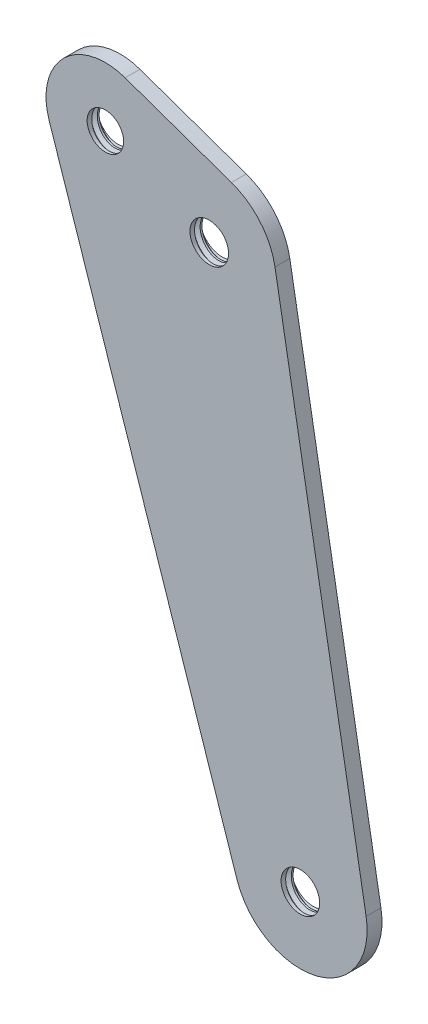
SolidWorks part; units mm, degrees
material "AISI 304"
ref_plane "Alzado" through (0, 0, 0) normal (0, 0, 1) x (1, 0, 0)
ref_plane "Planta" through (0, 0, 0) normal (0, 1, 0) x (1, 0, 0)
ref_plane "Vista lateral" through (0, 0, 0) normal (1, 0, 0) x (0, 0, -1)
ref_plane "Plano1" through (0, 0, 4.2) normal (0, 0, 1) x (1, 0, 0)
sketch "Sk_Placa_jaula_exterior" plane through (0, 0, 4.2) normal (0, 0, 1) x (1, 0, 0)
  line L0 (-43.5893, -64.5304) -> (-18.2523, -140.5219)
  line L1 (-0.8511, -136.1123) -> (-13.1367, -66.4372)
  line L2 (-19.0055, -59.5128) -> (-33.3382, -54.4558)
  arc A0 (-18.2523, -140.5219) -> (-0.8511, -136.1123) centre (-9.7144, -137.6751) ccw
  arc A1 (-13.1367, -66.4372) -> (-19.0055, -59.5128) centre (-22, -68) ccw
  arc A2 (-33.3382, -54.4558) -> (-43.5893, -64.5304) centre (-36, -62) ccw
  circle A3 centre (-36, -62) radius 2.46
  circle A4 centre (-22, -68) radius 2.6
  circle A5 centre (-9.7144, -137.6751) radius 2.6
extrude "Placa_jaula_exterior" add sketch "Sk_Placa_jaula_exterior" along normal blind 2
thread "Rosca_M6x1" pitch 1 method cut profile "Perfil de rosca1" start angle 135, offset 0, length 2, pitch 1, diameter 4.92
ref_plane "Plano2" through (-34.2605, -60.2605, 6.2) normal (-0.7071, 0.7071, 0) x (0.7071, 0.7071, 0)
sketch "Perfil de rosca1" plane through (-34.2605, -60.2605, 6.2) normal (-0.7071, 0.7071, 0) x (0.7071, 0.7071, 0)
  line L0 (0, 0) -> (0, 1) construction
  line L1 (0, 0) -> (0.5413, 0.3125)
  line L2 (0.5413, 0.3125) -> (0.5413, 0.4375)
  line L3 (0.5413, 0.4375) -> (0, 0.75)
  line L4 (0.5413, 0.375) -> (0, 0.375) construction
  line L11 (0, 0) -> (0, 0.75)
  point P2 (0, 0)
  dimension "Pitch" = 1
  dimension "Profile_Angle" = 60
  dimension "Profile_Land" = 0.125
  dimension "Profile_Height" = 0.5413
thread "Rosca1" pitch 1 method cut profile "Perfil de rosca2" start angle 135, offset 0, length 2, pitch 1, diameter 5.2
ref_plane "Plano3" through (-7.8759, -135.8367, 6.2) normal (-0.7071, 0.7071, 0) x (0.7071, 0.7071, 0)
sketch "Perfil de rosca2" plane through (-7.8759, -135.8367, 6.2) normal (-0.7071, 0.7071, 0) x (0.7071, 0.7071, 0)
  line L0 (0, 0) -> (0, 1) construction
  line L1 (0, 0) -> (0.5413, 0.3125)
  line L2 (0.5413, 0.3125) -> (0.5413, 0.4375)
  line L3 (0.5413, 0.4375) -> (0, 0.75)
  line L4 (0.5413, 0.375) -> (0, 0.375) construction
  line L11 (0, 0) -> (0, 0.75)
  point P2 (0, 0)
  dimension "Pitch" = 1
  dimension "Profile_Angle" = 60
  dimension "Profile_Land" = 0.125
  dimension "Profile_Height" = 0.5413
thread "Rosca2" pitch 1 method cut profile "Perfil de rosca3" start angle 135, offset 0, length 2, pitch 1, diameter 5.2
ref_plane "Plano4" through (-20.1615, -66.1615, 6.2) normal (-0.7071, 0.7071, 0) x (0.7071, 0.7071, 0)
sketch "Perfil de rosca3" plane through (-20.1615, -66.1615, 6.2) normal (-0.7071, 0.7071, 0) x (0.7071, 0.7071, 0)
  line L0 (0, 0) -> (0, 1) construction
  line L1 (0, 0) -> (0.5413, 0.3125)
  line L2 (0.5413, 0.3125) -> (0.5413, 0.4375)
  line L3 (0.5413, 0.4375) -> (0, 0.75)
  line L4 (0.5413, 0.375) -> (0, 0.375) construction
  line L11 (0, 0) -> (0, 0.75)
  point P2 (0, 0)
  dimension "Pitch" = 1
  dimension "Profile_Angle" = 60
  dimension "Profile_Land" = 0.125
  dimension "Profile_Height" = 0.5413
